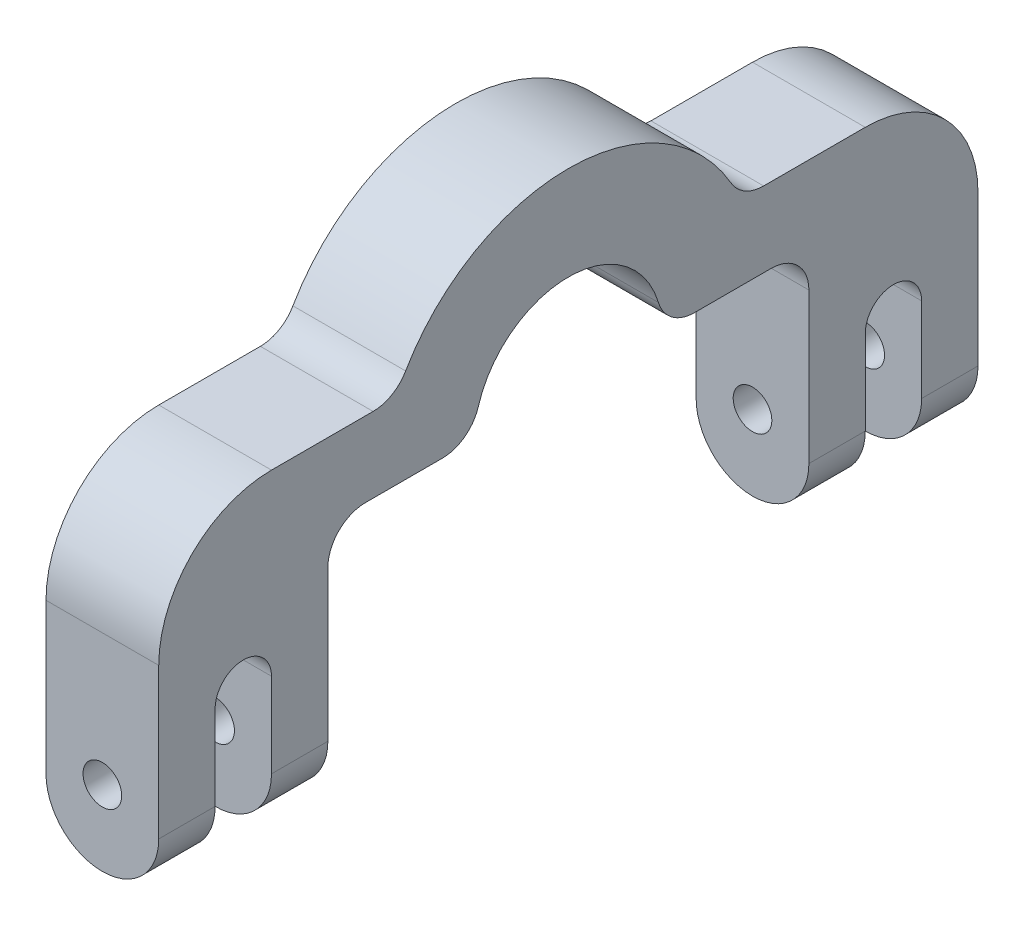
SolidWorks part; units mm, degrees
ref_plane "Front Plane" through (0, 0, 0) normal (0, 0, 1) x (1, 0, 0)
ref_plane "Top Plane" through (0, 0, 0) normal (0, 1, 0) x (1, 0, 0)
ref_plane "Right Plane" through (0, 0, 0) normal (1, 0, 0) x (0, 0, -1)
sketch "Sketch1" plane through (0, 0, 0) normal (0, 0, 1) x (1, 0, 0)
  line L0 (-4.7625, 0) -> (4.7625, 0)
  line L1 (-4.7625, 0) -> (-4.7625, -15.875)
  line L2 (4.7625, 0) -> (4.7625, -15.875)
  arc A0 (4.7625, -15.875) -> (-4.7625, -15.875) centre (0, -15.875) cw
  point P4 (0, 0)
  dimension "D1" = 4.7625
  dimension "D2" = 9.525
  dimension "D3" = 15.875
extrude "Boss-Extrude1" add sketch "Sketch1" along normal mid plane 69.215
sketch "Sketch2" plane through (0, 0, 34.6075) normal (0, 0, 1) x (1, 0, 0)
  line L0 (-4.7625, -15.875) -> (-4.7625, -6.35)
  line L1 (-4.7625, 0) -> (-4.7625, -15.875) construction
  line L2 (-4.7625, -6.35) -> (4.7625, -6.35)
  line L3 (4.7625, -15.875) -> (4.7625, 0) construction
  line L4 (4.7625, -6.35) -> (4.7625, -15.875)
  line L5 (4.7625, 0) -> (-4.7625, 0) construction
  arc A0 (-4.7625, -15.875) -> (4.7625, -15.875) centre (0, -15.875) ccw construction
  arc A1 (-4.7625, -15.875) -> (4.7625, -15.875) centre (0, -15.875) ccw
  dimension "D1" = 6.35
extrude "Cut-Extrude1" cut sketch "Sketch2" against normal blind 4.7625 from offset 4.7625 offset against normal yes
sketch "Sketch3" plane through (0, 0, -34.6075) normal (0, 0, 1) x (1, 0, 0)
  line L0 (-4.7625, -15.875) -> (-4.7625, -6.35)
  line L2 (-4.7625, -6.35) -> (4.7625, -6.35)
  line L4 (4.7625, -6.35) -> (4.7625, -15.875)
  line L6 (-4.7625, 0) -> (-4.7625, -15.875) construction
  line L7 (4.7625, -15.875) -> (4.7625, 0) construction
  line L8 (4.7625, 0) -> (-4.7625, 0) construction
  arc A1 (-4.7625, -15.875) -> (4.7625, -15.875) centre (0, -15.875) ccw
  arc A2 (-4.7625, -15.875) -> (4.7625, -15.875) centre (0, -15.875) ccw construction
  dimension "D1" = 6.35
extrude "Cut-Extrude2" cut sketch "Sketch3" along normal blind 4.7625 from offset 4.7625
sketch "Sketch5" plane through (0, 0, 25.0825) normal (0, 0, 1) x (1, 0, 0)
  line L3 (4.7625, -15.875) -> (4.7625, 0)
  line L4 (4.7625, 0) -> (-4.7625, 0)
  line L5 (-4.7625, 0) -> (-4.7625, -15.875)
  line L6 (4.7625, -15.875) -> (4.7625, 0)
  line L7 (4.7625, 0) -> (-4.7625, 0)
  line L8 (-4.7625, 0) -> (-4.7625, -15.875)
  arc A1 (-4.7625, -15.875) -> (4.7625, -15.875) centre (0, -15.875) ccw
  arc A2 (-4.7625, -15.875) -> (4.7625, -15.875) centre (0, -15.875) ccw
  dimension "D1" = 0
extrude "Cut-Extrude3" cut sketch "Sketch5" against normal offset from surface (40.64 mm away) 4.7625 from offset 4.7625 up to face at (0, -12.3031, -25.0825) offset against normal yes
sketch "Sketch7" plane through (0, 0, 0) normal (0, 0, 1) x (1, 0, 0)
  line L0 (4.7625, 0) -> (4.7625, 6.35)
  line L1 (4.7625, 6.35) -> (-4.7625, 6.35)
  line L2 (-4.7625, 6.35) -> (-4.7625, 0)
  line L3 (4.7625, 0) -> (-4.7625, 0)
  dimension "D1" = 6.35
extrude "Boss-Extrude3" add sketch "Sketch7" against normal up to surface (34.6075 mm away) from surface up to face at (0, -9.1281, -34.6075) starting at face at (0, -9.1281, 34.6075)
fillet "Fillet1" radius 3.175 2 edges at (0, 0, 20.32) (0, 0, -20.32)
fillet "Fillet2" 2 edges at (0, -6.35, -29.845) (0, -6.35, -25.0825) type full round first side face at (0, -12.3031, -29.845) second side face at (0, -12.3031, -25.0825) middle face at (0, -6.35, -27.4638)
fillet "Fillet3" 2 edges at (0, -6.35, 25.0825) (0, -6.35, 29.845) type full round first side face at (0, -12.3031, 25.0825) second side face at (0, -12.3031, 29.845) middle face at (0, -6.35, 27.4638)
sketch "Sketch8" plane through (-4.7625, 0, 0) normal (-1, 0, 0) x (0, 0, 1)
  line L0 (-34.6075, 6.35) -> (34.6075, 6.35) construction
  line L1 (-14.5497, 6.35) -> (14.5497, 6.35)
  arc A0 (-14.5497, 6.35) -> (14.5497, 6.35) centre (0, 0) cw
  dimension "D1" = 15.875
extrude "Boss-Extrude4" add sketch "Sketch8" against normal up to surface (9.525 mm away) up to face at (4.7625, -8.3054, 0)
sketch "Sketch9" plane through (-4.7625, 0, 0) normal (-1, 0, 0) x (0, 0, 1)
  line L0 (-17.145, 0) -> (17.145, 0) construction
  line L1 (-7.9375, 0) -> (7.9375, 0)
  arc A0 (-7.9375, 0) -> (7.9375, 0) centre (0, 0) cw
  dimension "D1" = 15.875
extrude "Cut-Extrude4" cut sketch "Sketch9" against normal through all
fillet "Fillet4" radius 3.175 4 edges at (0, 6.35, 14.5497) (0, 6.35, -14.5497) (0, 0, 7.9375) (0, 0, -7.9375)
fillet "Fillet5" radius 9.525 2 edges at (0, 6.35, 34.6075) (0, 6.35, -34.6075)
hole_wizard "#4 Clearance Hole1" positions "Sketch10" profile "Sketch11" hole size "#4" standard "ANSI Inch" end condition through all
sketch "Sketch10" plane through (0, 0, -34.6075) normal (0, 0, -1) x (-1, 0, 0)
  arc A0 (-4.7625, -15.875) -> (4.7625, -15.875) centre (0, -15.875) ccw construction
  point P0 (0, -14.2875)
  point P6 (0, -20.6375)
  dimension "D1" = 6.35
sketch "Sketch11" plane through (0, -14.2875, -34.6075) normal (1, 0, 0) x (0, 1, 0)
  line L0 (0, 0) -> (0, 69.215)
  line L1 (0, 69.215) -> (1.6319, 69.215)
  line L2 (1.6319, 69.215) -> (1.6319, 0)
  line L5 (1.6319, 0) -> (0, 0)
  line L11 (0, -6.35) -> (0, 107.95) construction
  dimension "Thru Hole Dia." = 3.2639
  dimension "Thru Hole Depth" = 69.215
